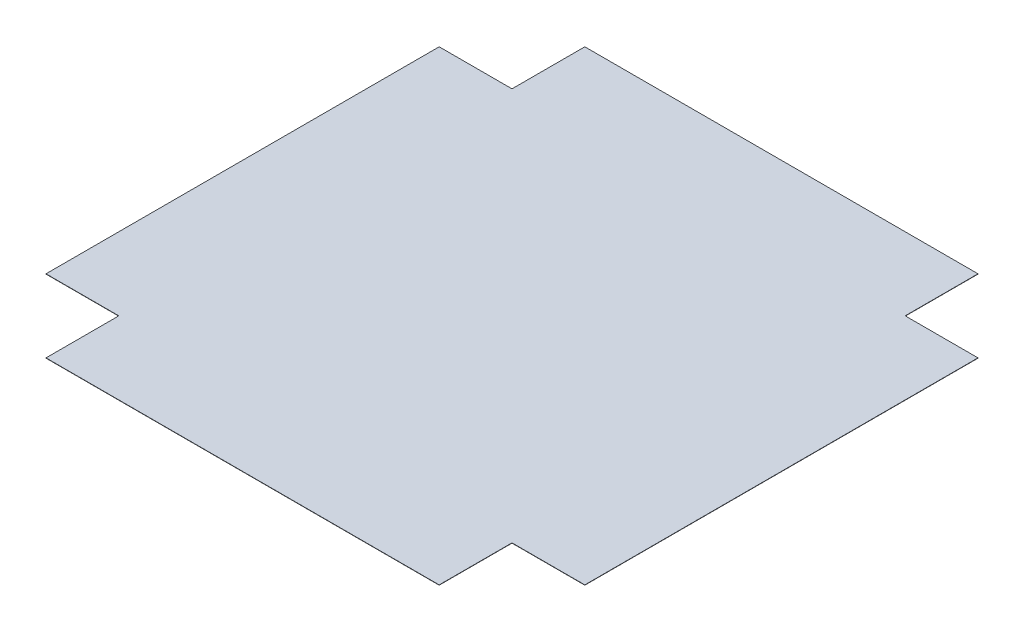
SolidWorks part; units mm, degrees
material "Corrugated Paper"
ref_plane "Front" through (0, 0, 0) normal (0, 0, 1) x (1, 0, 0)
ref_plane "Top" through (0, 0, 0) normal (0, 1, 0) x (1, 0, 0)
ref_plane "Right" through (0, 0, 0) normal (1, 0, 0) x (0, 0, -1)
ref_axis "X" through (-80.9, 0, 0) along (1, 0, 0)
ref_axis "Y" through (0, -50, 0) along (0, 1, 0)
ref_axis "Z" through (0, 0, -80.9) along (0, 0, 1)
sketch "Sketch1" plane through (0, 0, 0) normal (0, 1, 0) x (1, 0, 0)
  line L0 (-67.5, 92.5) -> (67.5, 92.5)
  line L1 (67.5, 92.5) -> (67.5, 67.5)
  line L2 (67.5, 67.5) -> (92.5, 67.5)
  line L3 (92.5, 67.5) -> (92.5, -67.5)
  line L4 (92.5, -67.5) -> (67.5, -67.5)
  line L5 (67.5, -67.5) -> (67.5, -92.5)
  line L6 (67.5, -92.5) -> (-67.5, -92.5)
  line L7 (-67.5, -92.5) -> (-67.5, -67.5)
  line L8 (-67.5, -67.5) -> (-92.5, -67.5)
  line L9 (-92.5, -67.5) -> (-92.5, 67.5)
  line L10 (-92.5, 67.5) -> (-67.5, 67.5)
  line L11 (-67.5, 67.5) -> (-67.5, 92.5)
  line L12 (-92.5, 0) -> (92.5, 0) construction
  line L13 (0, 92.5) -> (0, -92.5) construction
  dimension "D1" = 185
  dimension "D2" = 185
  dimension "D3" = 25
  dimension "D4" = 25
extrude "Boss-Extrude1" add sketch "Sketch1" along normal mid plane 0.1
sketch "Sketch2" plane through (0, -0.05, 0) normal (0, -1, 0) x (1, 0, 0)
  line L0 (67.5, 67.5) -> (43.5, 67.5)
  line L1 (67.5, 92.5) -> (67.5, 67.5) construction
  line L2 (43.5, 67.5) -> (43.5, 92.5)
  line L15 (-67.5, -67.5) -> (-67.5, -92.5)
  line L16 (-67.5, -92.5) -> (67.5, -92.5)
  line L17 (67.5, -92.5) -> (67.5, -67.5)
  line L18 (67.5, -67.5) -> (92.5, -67.5)
  line L19 (92.5, -67.5) -> (92.5, 67.5)
  line L20 (92.5, 67.5) -> (67.5, 67.5)
  line L21 (67.5, 67.5) -> (67.5, 92.5)
  line L22 (67.5, 92.5) -> (-67.5, 92.5)
  line L23 (-67.5, 92.5) -> (-67.5, 67.5)
  line L24 (-67.5, 67.5) -> (-92.5, 67.5)
  line L25 (-92.5, 67.5) -> (-92.5, -67.5)
  line L26 (-92.5, -67.5) -> (-67.5, -67.5)
  line L33 (67.5, 67.5) -> (67.5, 92.5)
  line L34 (67.5, 92.5) -> (43.5, 92.5)
  line M21 (67.5, 67.5) -> (67.5, 92.5)
  line M22 (67.5, 92.5) -> (-67.5, 92.5)
  dimension "D1" = 0
  dimension "D2" = 24
extrude "Cut-Extrude1" [suppressed] cut sketch "Sketch2" against normal through all contours L2 L0 M21 M22
